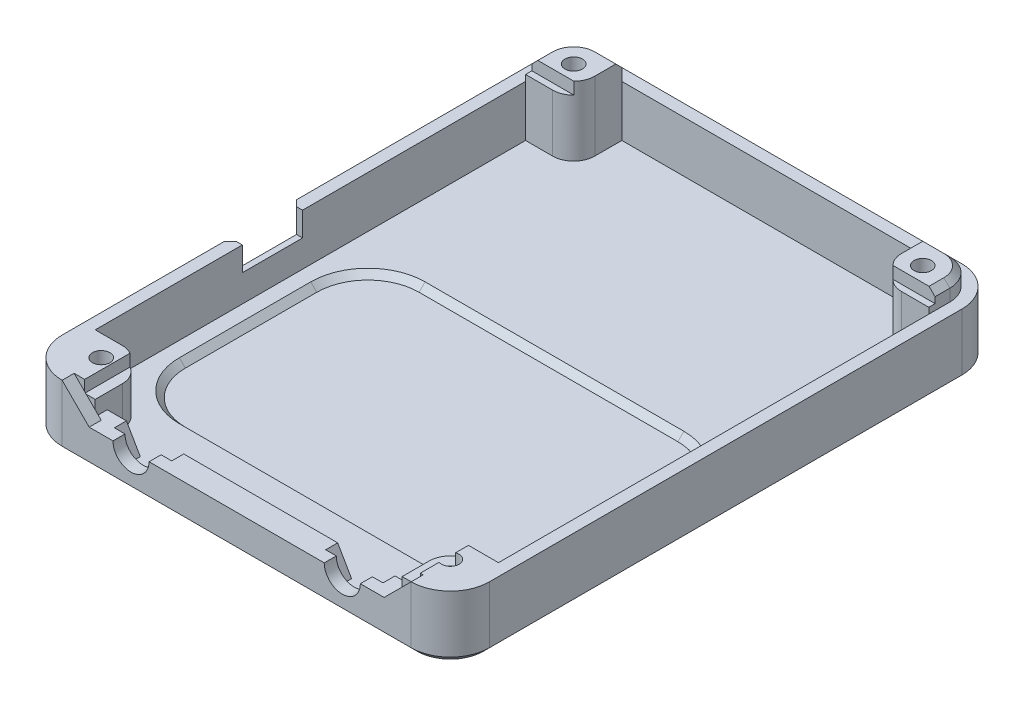
SolidWorks part; units mm, degrees
ref_plane "Front Plane" through (0, 0, 0) normal (0, 0, 1) x (1, 0, 0)
ref_plane "Top Plane" through (0, 0, 0) normal (0, 1, 0) x (1, 0, 0)
ref_plane "Right Plane" through (0, 0, 0) normal (1, 0, 0) x (0, 0, -1)
sketch "Sketch1" plane through (0, 0, 0) normal (0, 1, 0) x (1, 0, 0)
  line L0 (-33.8462, -25.5532) -> (31.1538, -25.5532)
  line L1 (-33.8462, 38.4468) -> (31.1538, 38.4468)
  line L2 (-33.8462, 38.4468) -> (-33.8462, 8.4468)
  line L3 (-33.8462, 8.4468) -> (31.1538, 8.4468)
  line L4 (31.1538, 38.4468) -> (31.1538, 8.4468)
  line L5 (-30.3462, 34.9468) -> (27.6538, 34.9468)
  line L6 (-30.3462, 34.9468) -> (-30.3462, 11.9468)
  line L7 (-30.3462, 11.9468) -> (27.6538, 11.9468)
  line L8 (27.6538, 34.9468) -> (27.6538, 11.9468)
  line L9 (-30.3462, 0.9468) -> (27.6538, 0.9468)
  line L10 (-30.3462, 0.9468) -> (-30.3462, -22.0532)
  line L11 (-33.8462, 4.4468) -> (31.1538, 4.4468)
  line L12 (-33.8462, 4.4468) -> (-33.8462, -25.5532)
  line L13 (-30.3462, -22.0532) -> (27.6538, -22.0532)
  line L14 (31.1538, 4.4468) -> (31.1538, -25.5532)
  line L15 (27.6538, 0.9468) -> (27.6538, -22.0532)
  line L16 (-37.9161, 25.3468) -> (-35.3276, 25.3468)
  line L17 (7.5538, 7.5472) -> (7.5538, 6.2645)
  line L18 (20.1538, 7.5472) -> (20.1538, 6.2645)
  dimension "D1" = 65
  dimension "D2" = 30
  dimension "D3" = 58
  dimension "D4" = 23
  dimension "D5" = 3.5
  dimension "D6" = 3.5
  dimension "D7" = 65
  dimension "D8" = 30
  dimension "D9" = 58
  dimension "D10" = 23
  dimension "D11" = 3.5
  dimension "D12" = 3.5
  dimension "D13" = 4
  dimension "D14" = 16.9
  dimension "D15" = 41.4
  dimension "D16" = 54
sketch "Sketch2" plane through (0, 0, 0) normal (0, 1, 0) x (1, 0, 0)
  line L0 (-33.8462, 38.4468) -> (-33.8462, 8.4468) construction
  line L1 (-30.3462, 39.4468) -> (27.6538, 39.4468)
  line L2 (-34.8462, 34.9468) -> (-34.8462, -43.5532)
  line L3 (-30.3462, -48.0532) -> (27.6538, -48.0532)
  line L4 (32.1538, 34.9468) -> (32.1538, -43.5532)
  line L5 (-33.8462, 38.4468) -> (31.1538, 38.4468) construction
  line L6 (31.1538, 38.4468) -> (31.1538, 8.4468) construction
  line L7 (-30.3462, 41.4468) -> (27.6538, 41.4468)
  line L8 (34.1538, 34.9468) -> (34.1538, -43.5532)
  line L9 (-30.3462, -50.0532) -> (27.6538, -50.0532)
  line L10 (-36.8462, 34.9468) -> (-36.8462, -43.5532)
  line L11 (-34.8462, 39.4468) -> (32.1538, 39.4468) construction
  line L12 (-34.8462, 39.4468) -> (-34.8462, -48.0532) construction
  line L13 (-36.8462, 41.4468) -> (-36.8462, -50.0532) construction
  line L14 (-36.8462, 41.4468) -> (34.1538, 41.4468) construction
  line L15 (32.1538, 39.4468) -> (32.1538, -48.0532) construction
  line L16 (34.1538, 41.4468) -> (34.1538, -50.0532) construction
  line L17 (-36.8462, -50.0532) -> (34.1538, -50.0532) construction
  line L18 (-34.8462, -48.0532) -> (32.1538, -48.0532) construction
  arc A0 (-30.3462, 39.4468) -> (-34.8462, 34.9468) centre (-30.3462, 34.9468) ccw
  arc A1 (-36.8462, 34.9468) -> (-30.3462, 41.4468) centre (-30.3462, 34.9468) cw
  arc A2 (32.1538, 34.9468) -> (27.6538, 39.4468) centre (27.6538, 34.9468) ccw
  arc A3 (34.1538, 34.9468) -> (27.6538, 41.4468) centre (27.6538, 34.9468) ccw
  arc A4 (27.6538, -50.0532) -> (34.1538, -43.5532) centre (27.6538, -43.5532) ccw
  arc A5 (-36.8462, -43.5532) -> (-30.3462, -50.0532) centre (-30.3462, -43.5532) ccw
  arc A6 (27.6538, -48.0532) -> (32.1538, -43.5532) centre (27.6538, -43.5532) ccw
  arc A7 (-30.3462, -48.0532) -> (-34.8462, -43.5532) centre (-30.3462, -43.5532) cw
  dimension "D6" = 4.5
  dimension "D7" = 6.5
  dimension "D8" = 4.5
  dimension "D9" = 6.5
  dimension "D10" = 6.5
  dimension "D11" = 4.5
  dimension "D1" = 1
  dimension "D2" = 1
  dimension "D3" = 1
  dimension "D4" = 87.5
  dimension "D5" = 2
extrude "Boss-Extrude1" add sketch "Sketch2" along normal blind 10.5
sketch "Sketch3" plane through (0, 0, 0) normal (0, 1, 0) x (1, 0, 0)
  line L0 (-30.3462, -48.0532) -> (27.6538, -48.0532)
  line L1 (-30.3462, 39.4468) -> (27.6538, 39.4468)
  line L2 (-34.8462, 34.9468) -> (-34.8462, -43.5532)
  line L4 (32.1538, 34.9468) -> (32.1538, -43.5532)
  arc A0 (27.6538, -48.0532) -> (32.1538, -43.5532) centre (27.6538, -43.5532) ccw
  arc A1 (-34.8462, -43.5532) -> (-30.3462, -48.0532) centre (-30.3462, -43.5532) ccw
  arc A2 (32.1538, 34.9468) -> (27.6538, 39.4468) centre (27.6538, 34.9468) ccw
  arc A3 (-30.3462, 39.4468) -> (-34.8462, 34.9468) centre (-30.3462, 34.9468) ccw
  point P15 (-34.8462, 39.4468)
  dimension "D1" = 4.5
  dimension "D2" = 87.5
extrude "Boss-Extrude2" add sketch "Sketch3" along normal blind 2
sketch "Sketch6" plane through (0, 2, 0) normal (0, 1, 0) x (1, 0, 0)
  line L3 (-34.8462, 34.9468) -> (-34.8462, -43.5532) construction
  line L5 (-26.8462, 34.9468) -> (-26.8462, 39.4468)
  line L6 (27.6538, 39.4468) -> (-30.3462, 39.4468) construction
  line L7 (-26.8462, 39.4468) -> (-30.3462, 39.4468)
  line L8 (-30.3462, 31.4468) -> (-34.8462, 31.4468)
  line L9 (-34.8462, 31.4468) -> (-34.8462, 34.9468)
  line L10 (24.1538, 34.9468) -> (24.1538, 39.4468)
  line L11 (24.1538, 39.4468) -> (27.6538, 39.4468)
  line L12 (27.6538, 31.4468) -> (32.1538, 31.4468)
  line L13 (32.1538, -43.5532) -> (32.1538, 34.9468) construction
  line L14 (32.1538, 31.4468) -> (32.1538, 34.9468)
  arc A0 (-30.3462, 31.4468) -> (-26.8462, 34.9468) centre (-30.3462, 34.9468) ccw
  arc A1 (24.1538, 34.9468) -> (27.6538, 31.4468) centre (27.6538, 34.9468) ccw
  arc A4 (-30.3462, 39.4468) -> (-34.8462, 34.9468) centre (-30.3462, 34.9468) ccw
  arc A5 (32.1538, 34.9468) -> (27.6538, 39.4468) centre (27.6538, 34.9468) ccw
  dimension "D1" = 4.5
  dimension "D2" = 4.5
extrude "Boss-Extrude4" add sketch "Sketch6" along normal blind 11.5
sketch "Sketch7" plane through (0, 0, 50.0532) normal (0, 0, 1) x (1, 0, 0)
  line L0 (27.6538, 10.5) -> (-30.3462, 10.5)
  line L2 (16.2046, 6) -> (16.2046, 3) construction
  line L3 (-18.8969, 6) -> (-18.8969, 3) construction
  line L4 (-1.3462, 10.5) -> (-1.3462, 13.2512) construction
  line L5 (-30.3462, 10.5) -> (27.6538, 10.5) construction
  line L20 (27.6538, 10.5) -> (23.1538, 6)
  line L21 (23.1538, 6) -> (19.2046, 6)
  line L22 (13.2046, 6) -> (-15.8969, 6)
  line L23 (-25.8462, 6) -> (-21.8969, 6)
  line L24 (-30.3462, 10.5) -> (-25.8462, 6)
  arc A0 (-21.8969, 6) -> (-15.8969, 6) centre (-18.8969, 6) ccw
  arc A1 (13.2046, 6) -> (19.2046, 6) centre (16.2046, 6) ccw
  dimension "D3" = 45
  dimension "D1" = 4.5
  dimension "D4" = 3
  dimension "D5" = 3
  dimension "D2" = 45
  dimension "D6" = 4.5
  dimension "D7" = 4.5
sketch "Sketch8" plane through (0, 2, 0) normal (0, 1, 0) x (1, 0, 0)
  line L9 (32.1538, -40.0532) -> (32.1538, -43.5532)
  line L10 (27.6538, -40.0532) -> (32.1538, -40.0532)
  line L11 (24.1538, -48.0532) -> (27.6538, -48.0532)
  line L12 (24.1538, -43.5532) -> (24.1538, -48.0532)
  line L13 (-34.8462, -40.0532) -> (-34.8462, -43.5532)
  line L14 (-30.3462, -40.0532) -> (-34.8462, -40.0532)
  line L15 (-26.8462, -48.0532) -> (-30.3462, -48.0532)
  line L16 (-26.8462, -43.5532) -> (-26.8462, -48.0532)
  arc A4 (32.1538, -43.5532) -> (27.6538, -48.0532) centre (27.6538, -43.5532) cw
  arc A5 (-30.3462, -48.0532) -> (-34.8462, -43.5532) centre (-30.3462, -43.5532) cw
  arc A6 (24.1538, -43.5532) -> (27.6538, -40.0532) centre (27.6538, -43.5532) cw
  arc A7 (-30.3462, -40.0532) -> (-26.8462, -43.5532) centre (-30.3462, -43.5532) cw
extrude "Boss-Extrude6" add sketch "Sketch8" along normal up to vertex (8.5 mm away) up to point (-34.8462, 10.5, 43.5532)
extrude "Cut-Extrude1" cut sketch "Sketch7" against normal up to vertex (2 mm away) up to point (-26.8462, 10.5, 48.0532)
sketch "Sketch9" plane through (-36.8462, 0, 0) normal (-1, 0, 0) x (0, 0, 1)
  line L1 (15.6113, 10.5) -> (5.6113, 10.5)
  line L2 (15.6113, 10.5) -> (15.6113, 6.5)
  line L3 (15.6113, 6.5) -> (5.6113, 6.5)
  line L4 (5.6113, 10.5) -> (5.6113, 6.5)
  line L5 (15.6113, 10.5) -> (5.6113, 6.5) construction
  line L6 (15.6113, 6.5) -> (5.6113, 10.5) construction
  point P0 (10.6113, 8.5)
  dimension "D1" = 10
  dimension "D2" = 4
extrude "Cut-Extrude2" cut sketch "Sketch9" against normal up to next
chamfer "Chamfer1" distance 1 angle 45 3 edges at (-36.8462, 8.5, 5.6113) (-36.8462, 8.5, 15.6113) (-36.8462, 6.5, 10.6113)
chamfer "Chamfer2" distance 1 angle 45 8 edges at (-36.8462, 0, 4.3032) (-34.9423, 0, 48.1493) (-34.9423, 0, -39.543) (-1.3462, 0, 50.0532) (-1.3462, 0, -41.4468) (32.25, 0, 48.1493) (32.25, 0, -39.543) (34.1538, 0, 4.3032)
hole_wizard "CBORE for M2.5 Pan Head Machine Screw1" positions "Sketch11" profile "Sketch10" counterbore size "M2.5" standard "ANSI Metric" end condition through all
sketch "Sketch11" plane through (0, 0, 0) normal (0, -1, 0) x (-1, 0, 0)
  point P0 (-27.6538, 34.9468)
sketch "Sketch10" plane through (27.6538, 0, -34.9468) normal (1, 0, 0) x (0, 0, -1)
  line L0 (0, 0) -> (0, 13.5)
  line L1 (0, 13.5) -> (1.45, 13.5)
  line L3 (1.45, 13.5) -> (1.45, 2.1)
  line L4 (1.45, 2.1) -> (3, 2.1)
  line L5 (3, 2.1) -> (3, 0)
  line L7 (3, 0) -> (0, 0)
  line L11 (0, -6.35) -> (0, 107.95) construction
  dimension "Thru Hole Dia." = 2.9
  dimension "Thru Hole Depth" = 13.5
  dimension "C'Bore Dia." = 6
  dimension "C'Bore Depth" = 2.1
hole_wizard "CBORE for M2.5 Pan Head Machine Screw2" positions "Sketch13" profile "Sketch12" counterbore size "M2.5" standard "ANSI Metric" end condition through all
sketch "Sketch13" plane through (0, 0, 0) normal (0, -1, 0) x (-1, 0, 0)
  point P0 (30.3462, 34.9468)
sketch "Sketch12" plane through (-30.3462, 0, -34.9468) normal (1, 0, 0) x (0, 0, -1)
  line L0 (0, 0) -> (0, 13.5)
  line L1 (0, 13.5) -> (1.45, 13.5)
  line L3 (1.45, 13.5) -> (1.45, 2.1)
  line L4 (1.45, 2.1) -> (3, 2.1)
  line L5 (3, 2.1) -> (3, 0)
  line L7 (3, 0) -> (0, 0)
  line L11 (0, -6.35) -> (0, 107.95) construction
  dimension "Thru Hole Dia." = 2.9
  dimension "Thru Hole Depth" = 13.5
  dimension "C'Bore Dia." = 6
  dimension "C'Bore Depth" = 2.1
hole_wizard "CBORE for M2.5 Pan Head Machine Screw3" positions "Sketch15" profile "Sketch14" counterbore size "M2.5" standard "ANSI Metric" end condition through all
sketch "Sketch15" plane through (0, 0, 0) normal (0, -1, 0) x (-1, 0, 0)
  point P0 (-27.6538, -43.5532)
sketch "Sketch14" plane through (27.6538, 0, 43.5532) normal (1, 0, 0) x (0, 0, -1)
  line L0 (0, 0) -> (0, 13.5)
  line L1 (0, 13.5) -> (1.45, 13.5)
  line L3 (1.45, 13.5) -> (1.45, 2.1)
  line L4 (1.45, 2.1) -> (3, 2.1)
  line L5 (3, 2.1) -> (3, 0)
  line L7 (3, 0) -> (0, 0)
  line L11 (0, -6.35) -> (0, 107.95) construction
  dimension "Thru Hole Dia." = 2.9
  dimension "Thru Hole Depth" = 13.5
  dimension "C'Bore Dia." = 6
  dimension "C'Bore Depth" = 2.1
hole_wizard "CBORE for M2.5 Pan Head Machine Screw4" positions "Sketch17" profile "Sketch16" counterbore size "M2.5" standard "ANSI Metric" end condition through all
sketch "Sketch17" plane through (0, 0, 0) normal (0, -1, 0) x (-1, 0, 0)
  point P0 (30.3462, -43.5532)
sketch "Sketch16" plane through (-30.3462, 0, 43.5532) normal (1, 0, 0) x (0, 0, -1)
  line L0 (0, 0) -> (0, 13.5)
  line L1 (0, 13.5) -> (1.45, 13.5)
  line L3 (1.45, 13.5) -> (1.45, 2.1)
  line L4 (1.45, 2.1) -> (3, 2.1)
  line L5 (3, 2.1) -> (3, 0)
  line L7 (3, 0) -> (0, 0)
  line L11 (0, -6.35) -> (0, 107.95) construction
  dimension "Thru Hole Dia." = 2.9
  dimension "Thru Hole Depth" = 13.5
  dimension "C'Bore Dia." = 6
  dimension "C'Bore Depth" = 2.1
sketch "Sketch18" plane through (0, 10.5, 0) normal (0, 1, 0) x (1, 0, 0)
  line L0 (-26.8462, -48.0532) -> (-30.3462, -48.0532) construction
  line L1 (-28.5962, -48.0532) -> (27.1698, -48.0532)
  line L2 (-28.5962, -48.0532) -> (-28.5962, -40.0868)
  line L3 (-28.5962, -40.0868) -> (27.1698, -40.0868)
  line L4 (27.1698, -48.0532) -> (27.1698, -40.0868)
  arc A0 (27.6538, -40.0532) -> (24.1538, -43.5532) centre (27.6538, -43.5532) ccw construction
extrude "Cut-Extrude3" cut sketch "Sketch18" against normal blind 2
sketch "Sketch19" plane through (0, 0, 48.0532) normal (0, 0, -1) x (-1, 0, 0)
  line L0 (24.6458, 6) -> (23.6607, 6)
  line L1 (14.1331, 6) -> (16.515, 1.8744)
  line L2 (16.515, 1.8744) -> (21.2788, 1.8744)
  line L3 (21.2788, 1.8744) -> (23.6607, 6)
  line L4 (-11.4408, 6) -> (-10.4558, 6)
  line L5 (-20.9684, 6) -> (-21.9535, 6)
  line L6 (24.6458, 6) -> (26.8462, 6)
  line L7 (-20.9684, 6) -> (-18.5865, 1.8744)
  line L8 (-18.5865, 1.8744) -> (-13.8227, 1.8744)
  line L9 (-13.8227, 1.8744) -> (-11.4408, 6)
  line L10 (26.8462, 7) -> (26.8462, 2) construction
  line L11 (26.8462, 6) -> (26.8462, 2)
  line L12 (26.8462, 2) -> (21.3513, 2)
  line L13 (13.1481, 6) -> (14.1331, 6)
  line L14 (26.8462, 2) -> (-24.1538, 2) construction
  line L15 (22.4698, 8.0628) -> (21.3151, 10.0628) [skipped]
  line L16 (16.3625, 9.8613) -> (15.2078, 7.8613) [skipped]
  line L17 (20.9737, 10.1256) -> (16.3549, 10.1256) [skipped]
  line L18 (-12.6318, 8.0628) -> (-13.7865, 10.0628) [skipped]
  line L19 (-16.2046, 10.1256) -> (-18.514, 10.1256) [skipped]
  line L20 (-18.7391, 9.8613) -> (-19.8938, 7.8613) [skipped]
  line L21 (13.1481, 6) -> (-10.4558, 6)
  line L22 (-21.9535, 6) -> (-24.1538, 6)
  line L23 (-24.1538, 7) -> (-24.1538, 2) construction
  line L24 (-24.1538, 6) -> (-24.1538, 2)
  line L25 (-24.1538, 2) -> (-18.659, 2)
  line L26 (-13.7502, 2) -> (16.4425, 2)
  arc A0 (15.3241, 3.9372) -> (22.4698, 3.9372) centre (18.8969, 6) ccw construction
  arc A1 (-19.7775, 3.9372) -> (-12.6318, 3.9372) centre (-16.2046, 6) ccw construction
  line M6 (-24.1538, 7) -> (-24.1538, 2)
  line M7 (-24.1538, 2) -> (26.8462, 2)
  line M8 (26.8462, 2) -> (26.8462, 7)
  line M10 (25.8462, 6) -> (21.8969, 6)
  line M12 (15.8969, 6) -> (-13.2046, 6)
  line M14 (-19.2046, 6) -> (-23.1538, 6)
extrude "Boss-Extrude7" add sketch "Sketch19" along normal blind 2 contours L22 L7 M14 M6 M7 | L9 L1 M7 M12 | L6 L3 M10 M7 M8 region at (-24.6249, 3.8226, 48.0532) region at (21.9326, 3.8226, 48.0532) region at (-1.3462, 3.9448, 48.0532)
sketch "Sketch21" plane through (0, 13.5, 0) normal (0, 1, 0) x (1, 0, 0)
  line L0 (-34.8462, 34.9468) -> (-34.8462, 31.4468) construction
  line L1 (-34.8462, 32.4905) -> (32.1538, 32.4905)
  line L2 (-34.8462, 32.4905) -> (-34.8462, 31.4468)
  line L3 (-34.8462, 31.4468) -> (32.1538, 31.4468)
  line L4 (32.1538, 32.4905) -> (32.1538, 31.4468)
extrude "Cut-Extrude4" cut sketch "Sketch21" against normal blind 2
sketch "Sketch22" plane through (0, 2, 0) normal (0, 1, 0) x (1, 0, 0)
  line L0 (-34.8462, 31.4468) -> (-34.8462, -40.0532) construction
  line L1 (-22.8462, 3.2594) -> (20.1538, 3.2594)
  line L2 (-32.8462, -6.7406) -> (-32.8462, -28.5682)
  line L3 (-22.8462, -38.5682) -> (20.1538, -38.5682)
  line L4 (30.1538, -6.7406) -> (30.1538, -28.5682)
  line L5 (32.1538, -40.0532) -> (32.1538, 31.4468) construction
  arc A0 (-22.8462, -38.5682) -> (-32.8462, -28.5682) centre (-22.8462, -28.5682) cw
  arc A1 (20.1538, -38.5682) -> (30.1538, -28.5682) centre (20.1538, -28.5682) ccw
  arc A2 (20.1538, 3.2594) -> (30.1538, -6.7406) centre (20.1538, -6.7406) cw
  arc A3 (-22.8462, 3.2594) -> (-32.8462, -6.7406) centre (-22.8462, -6.7406) ccw
  dimension "D3" = 10
  dimension "D1" = 2
  dimension "D2" = 2
extrude "Cut-Extrude5" cut sketch "Sketch22" against normal blind 1
chamfer "Chamfer4" distance 1.5 angle 45 8 edges at (-1.3462, 1, 38.5682) (27.2249, 1, 35.6392) (-29.9172, 1, 35.6392) (30.1538, 1, 17.6544) (-32.8462, 1, 17.6544) (27.2249, 1, -0.3305) (-29.9172, 1, -0.3305) (-1.3462, 1, -3.2594)
chamfer "Chamfer5" distance 1 angle 45 3 edges at (32.1538, 13.5, -33.7187) (25.9038, 13.5, -39.4468) (30.8358, 13.5, -38.1288)
chamfer "Chamfer6" distance 1 angle 45 3 edges at (-28.5962, 13.5, -39.4468) (-34.8462, 13.5, -33.7187) (-33.5281, 13.5, -38.1288)
